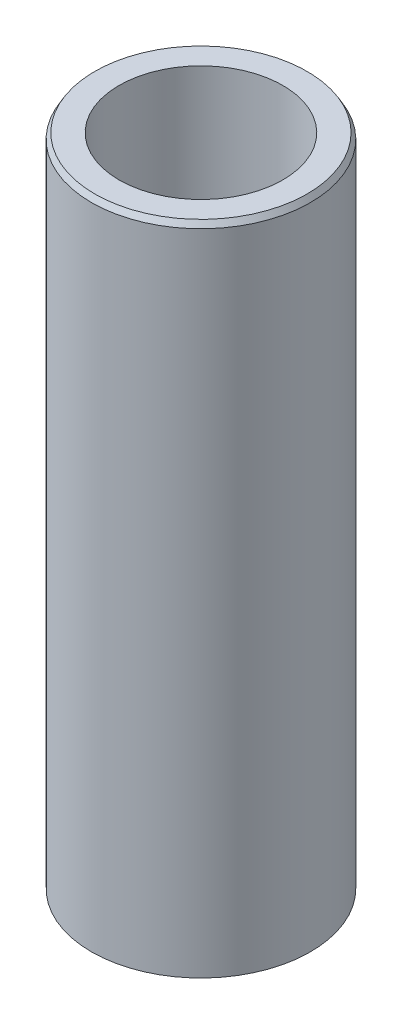
SolidWorks part; units mm, degrees
ref_plane "Front Plane" through (0, 0, 0) normal (0, 0, 1) x (1, 0, 0)
ref_plane "Top Plane" through (0, 0, 0) normal (0, 1, 0) x (1, 0, 0)
ref_plane "Right Plane" through (0, 0, 0) normal (1, 0, 0) x (0, 0, -1)
sketch "Sketch1" plane through (0, 0, 0) normal (0, 1, 0) x (1, 0, 0)
  circle A0 centre (0, 0) radius 15
  dimension "SHAFT_OD" = 30
extrude "Boss-Extrude1" add sketch "Sketch1" along normal blind 90.1346
sketch "Sketch2" plane through (0, 0, 0) normal (0, 1, 0) x (1, 0, 0)
  circle A0 centre (0, 0) radius 11.2185
  dimension "BORE_D" = 22.4371
extrude "Cut-Extrude1" cut sketch "Sketch2" along normal through all
chamfer "Chamfer1" distance 0.7905 angle 30 2 edges at (0, 90.1346, 15) (0, 0, 15) first distance on face at (0, 90.1346, 15) first distance on face at (0, 0, 11.2185)
